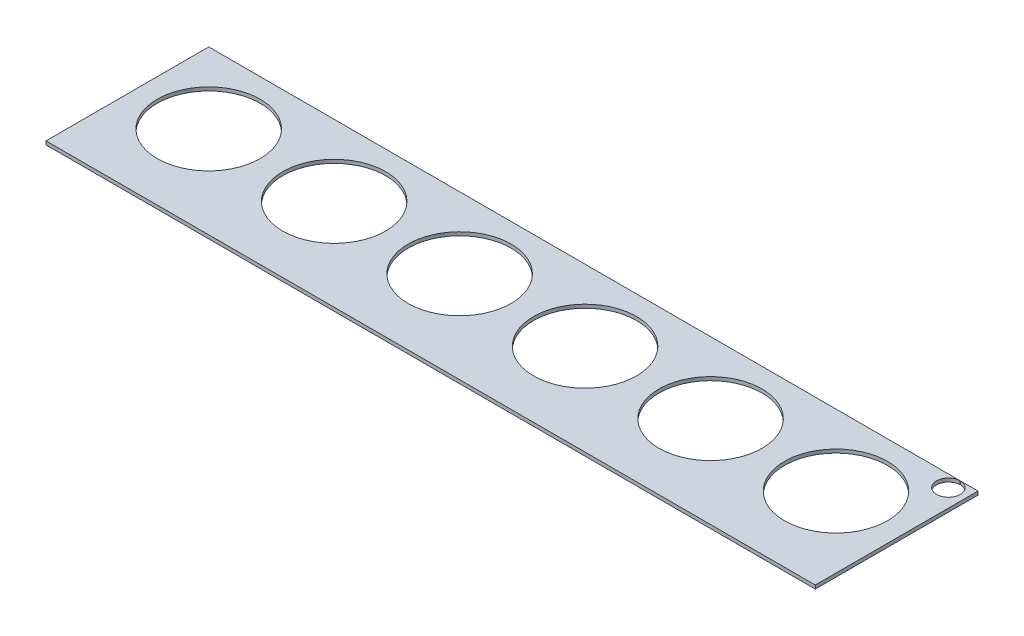
SolidWorks part; units mm, degrees
ref_plane "Front Plane" through (0, 0, 0) normal (0, 0, 1) x (1, 0, 0)
ref_plane "Top Plane" through (0, 0, 0) normal (0, 1, 0) x (1, 0, 0)
ref_plane "Right Plane" through (0, 0, 0) normal (1, 0, 0) x (0, 0, -1)
sketch "Sketch1" plane through (0, 0, 0) normal (0, 1, 0) x (1, 0, 0)
  line L1 (-296.8504, -10.9252) -> (353.1496, -10.9252)
  line L2 (-296.8504, -10.9252) -> (-296.8504, -148.4252)
  line L3 (-296.8504, -148.4252) -> (353.1496, -148.4252)
  line L4 (353.1496, -10.9252) -> (353.1496, -148.4252)
  dimension "D1" = 650
  dimension "D2" = 137.5
extrude "Boss-Extrude1" add sketch "Sketch1" along normal blind 3
sketch "Sketch2" plane through (0, 3, 0) normal (0, 1, 0) x (1, 0, 0)
  line L0 (-296.8504, -10.9252) -> (-296.8504, -148.4252) construction
  line L1 (353.1496, -10.9252) -> (-296.8504, -10.9252) construction
  line L2 (353.1496, -148.4252) -> (353.1496, -10.9252) construction
  circle A0 centre (-236.8504, -70.9252) radius 43.5
  circle A1 centre (-130.8504, -70.9252) radius 43.5
  circle A2 centre (-24.8504, -70.9252) radius 43.5
  circle A3 centre (81.1496, -70.9252) radius 43.5
  circle A5 centre (187.1496, -70.9252) radius 43.5
  circle A6 centre (293.1496, -70.9252) radius 43.5
  circle A7 centre (338.1496, -20.9242) radius 10
  dimension "D1" = 87
  dimension "D2" = 60
  dimension "D3" = 60
  dimension "D4" = 60
  dimension "D5" = 87
  dimension "D6" = 106
  dimension "D7" = 106
  dimension "D8" = 87
  dimension "D9" = 60
  dimension "D10" = 106
  dimension "D11" = 60
  dimension "D12" = 87
  dimension "D13" = 60
  dimension "D14" = 106
  dimension "D15" = 87
  dimension "D16" = 60
  dimension "D17" = 106
  dimension "D18" = 87
  dimension "D19" = 20
  dimension "D20" = 15
  dimension "D21" = 9.999
extrude "Cut-Extrude1" cut sketch "Sketch2" against normal through all contours A6 | A5 | A3 | A2 | A1 | A0
extrude "Cut-Extrude2" cut sketch "Sketch2<3>" against normal blind 10
sketch "Sketch2<3>" plane through (0, 3, 0) normal (0, 1, 0) x (1, 0, 0) same geometry as "Sketch2"
